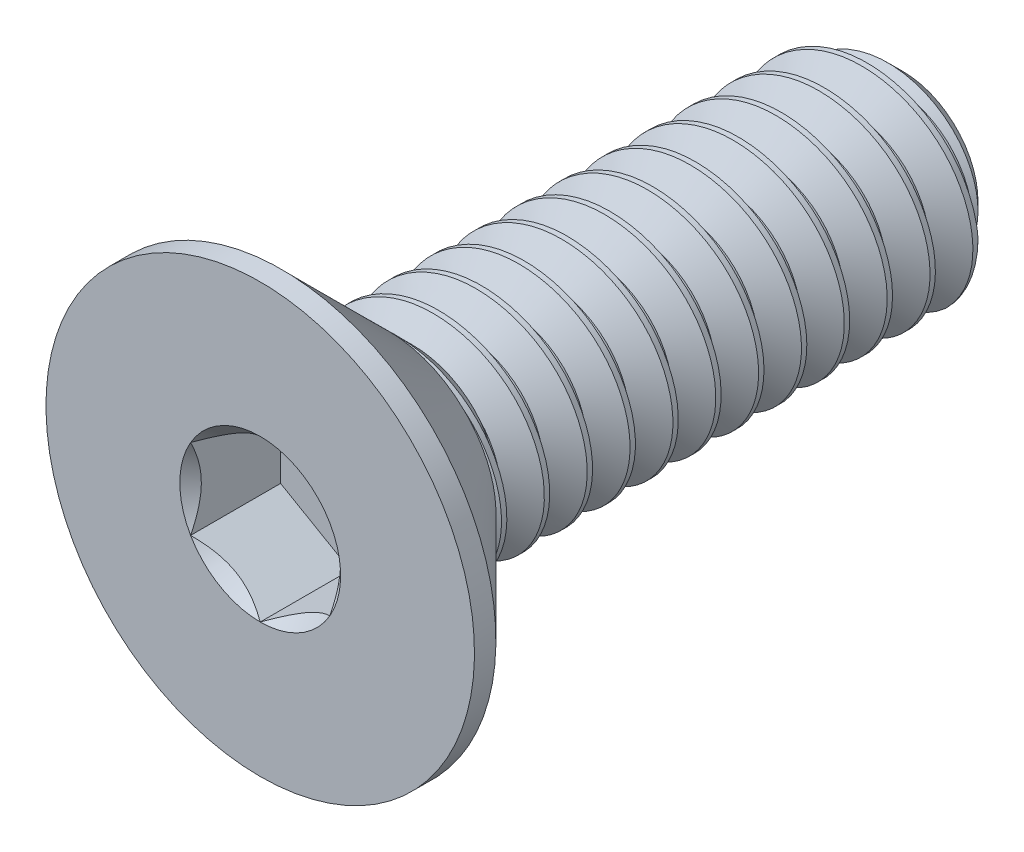
SolidWorks part; units mm, degrees
material "Alloy Steel"
ref_plane "Front" through (0, 0, 0) normal (0, 0, 1) x (1, 0, 0)
ref_plane "Top" through (0, 0, 0) normal (0, 1, 0) x (1, 0, 0)
ref_plane "Right" through (0, 0, 0) normal (1, 0, 0) x (0, 0, -1)
sketch "Sketch1" plane through (0, 0, 0) normal (1, 0, 0) x (0, 0, -1)
  line L0 (0, 2) -> (0.2, 2) construction
  line L1 (0.2, 2) -> (1.2, 1) construction
  line L2 (0, 1) -> (6, 1)
  line L3 (6, 1) -> (6, 0)
  line L4 (6, 0) -> (0, 0)
  line L5 (0, 0) -> (0, 2) construction
  line L6 (0, 2) -> (0, -2) construction
  line L7 (6, 1) -> (6, -1) construction
  line L8 (0, -2) -> (0.2, -2) construction
  line L9 (0.2, -2) -> (1.2, -1) construction
  line L11 (0, 1) -> (0, 0)
  line L12 (1.2, 1) -> (1.2, 0) construction
revolve "Revolve1" add sketch "Sketch1" angle 360 mid plane about L4
sketch "Sketch3" plane through (0, 0, -6) normal (0, 0, -1) x (-1, 0, 0)
  circle A0 centre (0, 0) radius 1
curve "Helix/Spiral1" pitch 0.4 height 6 radius 1 centre (0, 0, -6) axis (0, 0, 1) start towards (0, 1, 0)
sketch "Sketch2" plane through (0, 0, 0) normal (1, 0, 0) x (0, 0, -1)
  line L0 (6, 1) -> (6.35, 1)
  line L1 (6.35, 1) -> (6.2, 0.7402)
  line L2 (6.2, 0.7402) -> (6.15, 0.7402)
  line L3 (6.15, 0.7402) -> (6, 1)
  line L4 (6.075, 0.8701) -> (6.275, 0.8701) construction
  dimension "D1" = 60
  dimension "D2" = 0.05
  dimension "D3" = 0.2
chamfer "Chamfer1" distance 0.3 angle 45 1 edges at (0, 1, -6)
sweep "Cut-Sweep1" cut profiles "Sketch2" path "Helix/Spiral1" align with end faces yes
sketch "Sketch7" plane through (0, 0, 0) normal (1, 0, 0) x (0, 0, -1)
  line L0 (0, 2) -> (0.2, 2) construction
  line L1 (0.2, 2) -> (1.2, 1) construction
  line L2 (0, 2) -> (0.2, 2)
  line L3 (0.2, 2) -> (1.2, 1)
  line L4 (1.2, 1) -> (1.2, 0) construction
  line L5 (1.2, 1) -> (1.2, 0)
  line L7 (0, 0) -> (0, 2) construction
  line L8 (0, 0) -> (0, 2)
  line L9 (0, 0) -> (1.2, 0)
  line L10 (2.2, 0) -> (-2.2, 0) construction
revolve "Revolve2" add sketch "Sketch7" angle 360 mid plane about L9
ref_plane "Plane1" through (0, 0, -1.2) normal (0, 0, 1) x (1, 0, 0)
sketch "Sketch8" plane through (0, 0, -1.2) normal (0, 0, 1) x (1, 0, 0)
  circle A0 centre (0, 0) radius 1
extrude "Boss-Extrude1" add sketch "Sketch8" against normal through all draft 45
sketch "Sketch5" plane through (0, 0, 0) normal (0, 0, 1) x (1, 0, 0)
  line L1 (0.65, -0.3753) -> (0.65, 0.3753)
  line L2 (0.65, 0.3753) -> (0, 0.7506)
  line L3 (0, 0.7506) -> (-0.65, 0.3753)
  line L4 (-0.65, 0.3753) -> (-0.65, -0.3753)
  line L5 (-0.65, -0.3753) -> (0, -0.7506)
  line L6 (0, -0.7506) -> (0.65, -0.3753)
  circle A0 centre (0, 0) radius 0.65 construction
  dimension "Hex" = 1.3
extrude "Cut-Extrude2" cut sketch "Sketch5" against normal blind 0.84
sketch "Sketch6" plane through (0, 0, 0) normal (0, 0, 1) x (1, 0, 0)
  circle A0 centre (0, 0) radius 0.7506
extrude "Cut-Extrude3" cut sketch "Sketch6" against normal blind 0.84 draft 45
sketch "Sketch9" [suppressed] plane through (0, 0, -5.5) normal (0, 0, 1) x (1, 0, 0)
  circle A1 centre (0, 0) radius 5
  circle A2 centre (0, 0) radius 5
  point P0 (0, 5)
  dimension "D1" = 0
extrude "Boss-Extrude2" [suppressed] add sketch "Sketch9" against normal offset from surface (18.5 mm away) 26 up to face at (0, 0.7, -6)
fillet "Fillet1" [suppressed] radius 0.2
sketch "Sketch10" plane through (0, 0, 0) normal (1, 0, 0) x (0, 0, -1)
  line L0 (6, 1) -> (6, -1) construction
  point P0 (5.4, -1)
  dimension "D1" = 0.6
equation "\"D3@Helix/Spiral1\" = \"Lg@Sketch1\""
equation "\"D2@Sketch2\" = \"D4@Helix/Spiral1\" * .125"
equation "\"D3@Sketch2\" = \"D4@Helix/Spiral1\" * .5"
equation "\"D1@Chamfer1\" = \"D4@Helix/Spiral1\" * .75"
equation "\"D1@Cut-Extrude2\" = \"Head Ht@Sketch1\" * .7"
equation "\"D1@Sketch10\" = \"D4@Helix/Spiral1\" * 1.5"
equation "\"D1@Cut-Extrude3\" = \"D1@Cut-Extrude2\""
equation "\"D1@Fillet1\" = \"Dia@Sketch1\" * .1"
